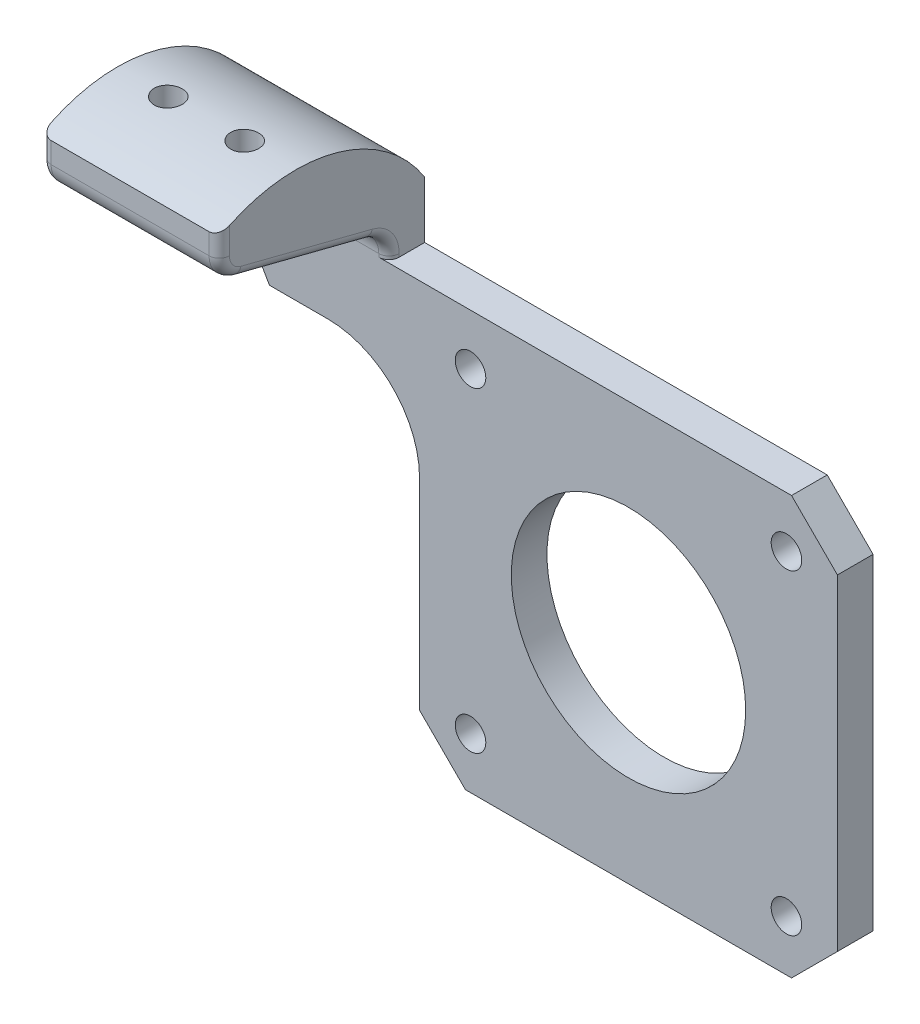
SolidWorks part; units mm, degrees
ref_plane "Front plane" through (0, 0, 0) normal (0, 0, 1) x (1, 0, 0)
ref_plane "Top plane" through (0, 0, 0) normal (0, 1, 0) x (1, 0, 0)
ref_plane "Right Plane" through (0, 0, 0) normal (1, 0, 0) x (0, 0, -1)
sketch "Sketch1" plane through (0, 0, 0) normal (0, 0, 1) x (1, 0, 0)
  line L0 (-15.5, 15.5) -> (-15.5, -15.5) construction
  line L1 (-15.5, -15.5) -> (15.5, -15.5) construction
  line L2 (-20.5, -16) -> (-16, -20.5)
  line L3 (-23.5, 20.5) -> (16, 20.5)
  line L4 (-20.5, 3.75) -> (-20.5, -16)
  line L5 (-16, -20.5) -> (16, -20.5)
  line L6 (20.5, 16) -> (20.5, -16)
  line L7 (16, -20.5) -> (20.5, -16)
  line L8 (16, 20.5) -> (20.5, 16)
  line L9 (-41, 33) -> (-23.5, 33)
  line L10 (-23.5, 33) -> (-23.5, 20.5)
  line L11 (-29.5, 12.75) -> (-35.2265, 12.75)
  line L12 (-35.2265, 12.75) -> (-41, 22.75)
  line L13 (-41, 22.75) -> (-41, 33)
  circle A0 centre (0, 0) radius 11.5
  circle A1 centre (-15.5, 15.5) radius 1.5
  circle A2 centre (15.5, 15.5) radius 1.5
  circle A3 centre (15.5, -15.5) radius 1.5
  circle A4 centre (-15.5, -15.5) radius 1.5
  arc A5 (-20.5, 3.75) -> (-29.5, 12.75) centre (-29.5, 3.75) ccw
  circle A7 centre (-30, 20.7462) radius 1.5
  point P5 (-15.5, 0)
  point P7 (0, -15.5)
  point P17 (0, -20.5)
  point P18 (20.5, 0)
  dimension "D1" = 23
  dimension "D3" = 3
  dimension "D7" = 9
  dimension "D2" = 31
  dimension "D4" = 4.5
  dimension "D5" = 41
  dimension "D6" = 24.25
  dimension "D8" = 3
  dimension "D9" = 9.5
  dimension "D12" = 120
  dimension "D13" = 17.5
  dimension "D14" = 12.5
  dimension "D15" = 10
  dimension "D10" = 20.7462
extrude "Boss-Extrude1" add sketch "Sketch1" along normal blind 3.5
sketch "Sketch2" plane through (-41, 0, 0) normal (-1, 0, 0) x (0, 0, 1)
  line L0 (3.5, 33) -> (20.15, 33)
  line L1 (20.15, 33) -> (20.15, 27)
  line L2 (20.15, 27) -> (3.5, 22.75)
  line L4 (3.5, 22.75) -> (3.5, 33)
  line L5 (3.5, 22.75) -> (0, 22.75) construction
  dimension "D1" = 16.65
  dimension "D2" = 6
extrude "Boss-Extrude2" add sketch "Sketch2" against normal up to vertex (17.5 mm away) up to point (-23.5, 33, 3.5)
sketch "Sketch3" plane through (-41, 0, 0) normal (-1, 0, 0) x (0, 0, 1)
  line L0 (20.15, 27) -> (20.15, 33) construction
  line L1 (0, 33) -> (0, 22.75) construction
  line L2 (20.15, 33) -> (0, 33) construction
  line L3 (12.65, 18) -> (12.65, 33) construction
  line L4 (0, 26.0609) -> (0, 38.0458)
  line L5 (0, 38.0458) -> (20.15, 38.0458)
  line L6 (20.15, 38.0458) -> (20.15, 30.9904)
  arc A0 (20.15, 30.9904) -> (0, 26.0609) centre (12.65, 18) ccw
  dimension "D2" = 15
  dimension "D1" = 7.5
extrude "Cut-Extrude1" cut sketch "Sketch3" against normal through all
sketch "Sketch4" plane through (0, -20.5, -236.3635) normal (0, 1, 0) x (1, 0, 0)
  line L0 (-36, -249.0135) -> (-28.5, -249.0135) construction
  line L1 (-32.25, -256.5135) -> (-32.25, -249.0135) construction
  line L2 (-41, -256.5135) -> (-23.5, -256.5135) construction
  circle A0 centre (-36, -249.0135) radius 1.375
  circle A1 centre (-28.5, -249.0135) radius 1.375
  dimension "D1" = 2.75
  dimension "D2" = 7.5
extrude "Cut-Extrude2" cut sketch "Sketch4" along normal through all
fillet "Fillet1" radius 2.5 2 edges at (-32.25, 27, 20.15) (-32.25, 22.75, 3.5)
fillet "Fillet2" radius 1 10 edges at (-41, 23.0419, 4.8777) (-41, 29.9662, 20.15) (-41, 27.4084, 19.6243) (-23.5, 20.654, 3.5) (-23.5, 22.3416, 4.0257) (-23.5, 29.9662, 20.15) (-23.5, 27.4084, 19.6243) (-41, 24.875, 11.825) (-23.5, 24.875, 11.825) (-41, 22.75, 2.2128)
equation "\"D10@Sketch1\"=20/pi+0.38+14"
